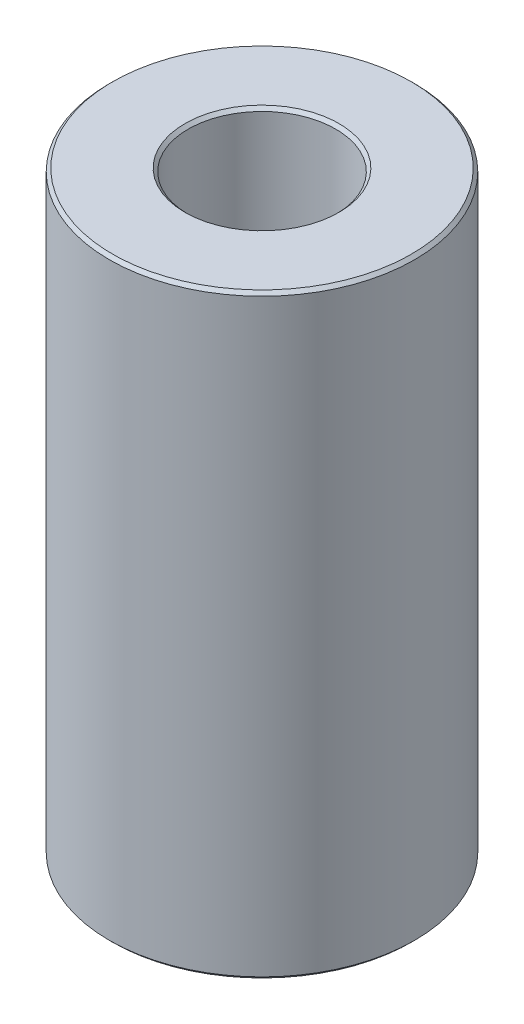
SolidWorks part; units mm, degrees
ref_plane "Front Plane" through (0, 0, 0) normal (0, 0, 1) x (1, 0, 0)
ref_plane "Top Plane" through (0, 0, 0) normal (0, 1, 0) x (1, 0, 0)
ref_plane "Right Plane" through (0, 0, 0) normal (1, 0, 0) x (0, 0, -1)
sketch "Sketch1" plane through (0, 0, 0) normal (0, 1, 0) x (1, 0, 0)
  circle A0 centre (0, 0) radius 45
  dimension "SLEEVE_OD" = 90
extrude "Boss-Extrude1" add sketch "Sketch1" along normal blind 175.7355
sketch "Sketch2" plane through (0, 0, 0) normal (0, 1, 0) x (1, 0, 0)
  circle A0 centre (0, 0) radius 21.7609
  dimension "BORE_D" = 43.5219
extrude "Cut-Extrude1" cut sketch "Sketch2" along normal through all
chamfer "Chamfer1" distance 0.9461 angle 45 4 edges at (0, 175.7355, 21.7609) (0, 0, 21.7609) (0, 0, 45) (0, 175.7355, 45)
